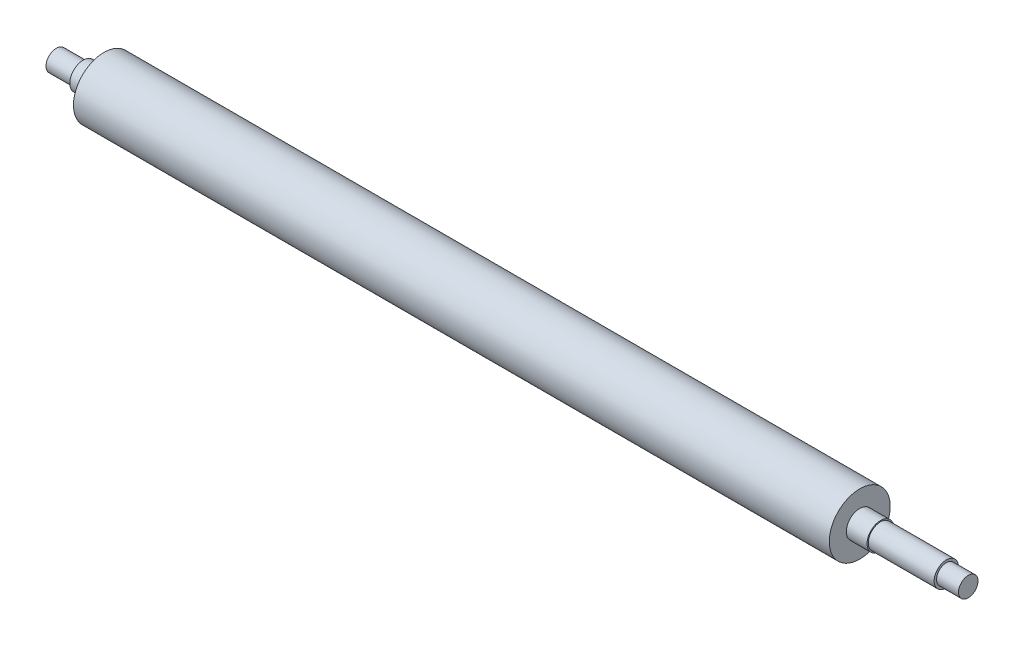
SolidWorks part; units mm, degrees
ref_plane "前视基准面" through (0, 0, 0) normal (0, 0, 1) x (1, 0, 0)
ref_plane "上视基准面" through (0, 0, 0) normal (0, 1, 0) x (1, 0, 0)
ref_plane "右视基准面" through (0, 0, 0) normal (1, 0, 0) x (0, 0, -1)
sketch "草图1" plane through (0, 0, 0) normal (0, 0, 1) x (1, 0, 0)
  line L0 (-230.7094, 0) -> (459.7941, 0) construction
  line L1 (0, 215.5466) -> (0, -189.8195) construction
  line L2 (-310, 25) -> (310, 25)
  line L6 (-349, 8.5) -> (-349, 0)
  line L7 (-327, 8.5) -> (-349, 8.5)
  line L8 (-310, 25) -> (-310, 11)
  line L9 (-349, 0) -> (399, 0)
  line L10 (-327, 8.5) -> (-327, 11)
  line L11 (-327, 11) -> (-310, 11)
  line L14 (327, 10) -> (327, 11)
  line L15 (327, 11) -> (310, 11)
  line L16 (310, 25) -> (310, 11)
  line L17 (327, 10) -> (381, 10)
  line L20 (381, 10) -> (381, 8)
  line L21 (381, 8) -> (399, 8)
  line L22 (399, 8) -> (399, 0)
  point P17 (0, 25)
  dimension "D1" = 11
  dimension "D2" = 8.5
  dimension "D3" = 25
  dimension "D4" = 620
  dimension "D5" = 22
  dimension "D6" = 17
  dimension "D7" = 17
  dimension "D8" = 18
  dimension "D9" = 8
  dimension "D10" = 10
  dimension "D11" = 54
revolve "旋转1" add sketch "草图1" angle 360 about L9
ref_plane "基准面1" through (0, -8, 0) normal (0, -1, 0) x (-1, 0, 0)
sketch "草图3" plane through (0, -8, 0) normal (0, -1, 0) x (-1, 0, 0)
  line L0 (-394, 0) -> (-386, 0) construction
  line L1 (-394, 3) -> (-386, 3)
  line L2 (-394, -3) -> (-386, -3)
  line L4 (-381, 10) -> (-381, -10) construction
  line L5 (-327, 10) -> (-381, 10) construction
  line L7 (-399, 8) -> (-399, -8) construction
  arc A0 (-394, 3) -> (-394, -3) centre (-394, 0) ccw
  arc A1 (-386, -3) -> (-386, 3) centre (-386, 0) ccw
  point P2 (-390, 0)
  point P9 (-389.0294, 0)
  dimension "D1" = 10
  dimension "D2" = 5
  dimension "D3" = 5
  dimension "D4" = 6
extrude "切除-拉伸1" cut sketch "草图3" against normal blind 3.5 contours L2 A1 L1 A0
